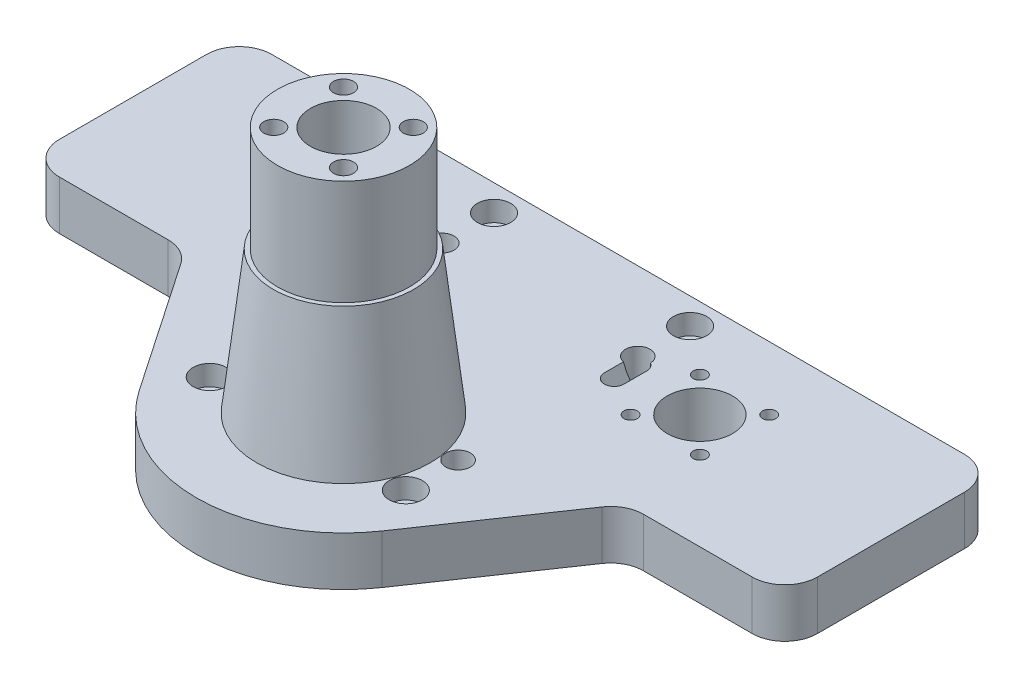
SolidWorks part; units mm, degrees
material "PLA Infill"
ref_plane "Front Plane" through (0, 0, 0) normal (0, 0, 1) x (1, 0, 0)
ref_plane "Top Plane" through (0, 0, 0) normal (0, 1, 0) x (1, 0, 0)
ref_plane "Right Plane" through (0, 0, 0) normal (1, 0, 0) x (0, 0, -1)
sketch "Sketch1" plane through (0, 0, 0) normal (0, 1, 0) x (1, 0, 0)
  line L0 (0, 0) -> (55, 54.0672) construction
  line L1 (55, 54.0672) -> (-55, 54.0672) construction
  line L2 (-55, 54.0672) -> (0, 0) construction
  line L3 (-79.7903, 37.1722) -> (-37.1854, -25.3425) construction
  line L4 (-55, 84.0672) -> (55, 84.0672)
  line L5 (37.1854, -25.3425) -> (79.7903, 37.1722) construction
  line L6 (-55, 84.0672) -> (-106, 84.0672)
  line L7 (-116, 74.0672) -> (-116, 29.0672)
  line L8 (-106, 19.0672) -> (-72.7378, 19.0672)
  line L9 (-64.4743, 14.6989) -> (-37.1854, -25.3425)
  line L10 (0, -1000) -> (0, 49000) construction
  line L11 (64.4743, 14.6989) -> (37.1854, -25.3425)
  line L12 (106, 19.0672) -> (72.7378, 19.0672)
  line L13 (116, 74.0672) -> (116, 29.0672)
  line L14 (55, 84.0672) -> (106, 84.0672)
  circle A0 centre (-55, 54.0672) radius 30 construction
  circle A1 centre (55, 54.0672) radius 30 construction
  circle A2 centre (0, 0) radius 45 construction
  arc A3 (-79.7903, 37.1722) -> (-55, 84.0672) centre (-55, 54.0672) cw construction
  arc A4 (55, 84.0672) -> (79.7903, 37.1722) centre (55, 54.0672) cw construction
  arc A5 (-37.1854, -25.3425) -> (37.1854, -25.3425) centre (0, 0) ccw
  arc A6 (-72.7378, 19.0672) -> (-64.4743, 14.6989) centre (-72.7378, 9.0672) cw
  arc A7 (-116, 29.0672) -> (-106, 19.0672) centre (-106, 29.0672) ccw
  arc A8 (-106, 84.0672) -> (-116, 74.0672) centre (-106, 74.0672) ccw
  arc A9 (72.7378, 19.0672) -> (64.4743, 14.6989) centre (72.7378, 9.0672) ccw
  arc A10 (116, 29.0672) -> (106, 19.0672) centre (106, 29.0672) cw
  arc A11 (106, 84.0672) -> (116, 74.0672) centre (106, 74.0672) cw
  point P23 (-67.4514, 19.0672)
  dimension "D3" = 60
  dimension "D4" = 90
  dimension "D5" = 10
  dimension "D6" = 61
  dimension "D1" = 110
  dimension "D2" = 77.125
  dimension "D7" = 35
extrude "Main Body" add sketch "Sketch1" along normal blind 15 contours A5 L11 A9 L12 A10 L13 A11 L14 L4 L6 A8 L7 A7 L8 A6 L9
sketch "Sketch3" plane through (0, 15, 0) normal (0, 1, 0) x (1, 0, 0)
  circle A0 centre (0, 0) radius 45 construction
  circle A1 centre (0, 0) radius 45 construction
  circle A2 centre (0, 0) radius 21.5
  dimension "D1" = 43
extrude "Front Extrusion" add sketch "Sketch3" along normal blind 75.7
ref_plane "First Bearing Section" through (0, 58.5, 0) normal (0, 1, 0) x (1, 0, 0)
sketch "Front Loft" plane through (0, 58.5, 0) normal (0, 1, 0) x (1, 0, 0)
  circle A0 centre (0, 0) radius 21.5
  dimension "D1" = 43
sketch "Back Loft" plane through (0, 15, 0) normal (0, 1, 0) x (1, 0, 0)
  circle A0 centre (0, 0) radius 26.5
  dimension "D1" = 53
loft "Lofted Taper" add profiles "Front Loft", "Back Loft" connector at (0, 58.5, 21.5) connector at (0, 15, 26.5)
sketch "Sketch4" plane through (0, 0, 0) normal (0, -1, 0) x (1, 0, 0)
  line L0 (0, -1000) -> (0, 49000) construction
  line L1 (-45, 0) -> (45, 0) construction
  line L2 (-85, -54.0672) -> (-25, -54.0672) construction
  line L3 (55, -54.0672) -> (-55, -54.0672) construction
  line L4 (-55, -24.0672) -> (-55, -84.0672) construction
  line L5 (-10.6773, 10.6773) -> (0, 0) construction
  line L6 (-10.6773, -10.6773) -> (0, 0) construction
  line L7 (-65.6066, -43.4606) -> (-55, -54.0672) construction
  line L8 (-106, -84.0672) -> (106, -84.0672) construction
  line L9 (106, -84.0672) -> (-106, -84.0672) construction
  line L10 (-30, -76.0672) -> (0, -76.0672) construction
  line L11 (-30, -76.0672) -> (-30, 10.9328) construction
  line L12 (-30, 10.9328) -> (0, 10.9328) construction
  line L13 (0, -76.0672) -> (0, 10.9328) construction
  circle A0 centre (55, -54.0672) radius 30 construction
  circle A1 centre (0, 0) radius 45 construction
  circle A2 centre (-55, -54.0672) radius 30 construction
  circle A3 centre (55, -54.0672) radius 30 construction
  circle A4 centre (0, 0) radius 45 construction
  circle A5 centre (-55, -54.0672) radius 30 construction
  circle A6 centre (0, 0) radius 10.1
  circle A7 centre (-55, -54.0672) radius 10
  circle A10 centre (-10.6773, 10.6773) radius 3.05
  circle A12 centre (-30, -60.0672) radius 3.75
  circle A13 centre (-10.6773, -10.6773) radius 3.05
  circle A14 centre (-65.6066, -43.4606) radius 2.05
  circle A15 centre (-65.6066, -64.6738) radius 2.05
  circle A16 centre (-44.3934, -64.6738) radius 2.05
  circle A17 centre (-44.3934, -43.4606) radius 2.05
  circle A18 centre (55, -54.0672) radius 10
  circle A19 centre (65.6066, -64.6738) radius 2.05
  circle A20 centre (44.3934, -64.6738) radius 2.05
  circle A21 centre (44.3934, -43.4606) radius 2.05
  circle A22 centre (65.6066, -43.4606) radius 2.05
  circle A23 centre (10.6773, -10.6773) radius 3.05
  circle A24 centre (10.6773, 10.6773) radius 3.05
  circle A25 centre (-30, -76.0672) radius 3.05
  circle A26 centre (-30, 10.9328) radius 3.05
  circle A27 centre (30, -76.0672) radius 3.05
  circle A28 centre (30, 10.9328) radius 3.05
  circle A29 centre (-30, -5.0672) radius 3.75
  circle A30 centre (30, -60.0672) radius 3.75
  circle A31 centre (30, -5.0672) radius 3.75
  dimension "D1" = 20.2
  dimension "D2" = 20
  dimension "D4" = 6.1
  dimension "D5" = 45
  dimension "D7" = 4.1
  dimension "D9" = 6.1
  dimension "D13" = 7.5
  dimension "D3" = 15.1
  dimension "D6" = 15
  dimension "D8" = 45
  dimension "D10" = 30
  dimension "D11" = 8
  dimension "D12" = 87
  dimension "D14" = 16
  dimension "D15" = 16
extrude "Bolt Holes" cut sketch "Sketch4" against normal through all
sketch "Sketch5" plane through (0, 0, 0) normal (0, -1, 0) x (1, 0, 0)
  line L0 (-14.2836, 7.0711) -> (-9.7707, 2.5582)
  line L1 (-7.0711, 14.2836) -> (-2.5582, 9.7707)
  line L2 (-10.6773, 10.6773) -> (0, 0) construction
  line L3 (-1000, 0) -> (49000, 0) construction
  line L4 (0, -1000) -> (0, 49000) construction
  line L5 (-14.2836, -7.0711) -> (-9.7707, -2.5582)
  line L6 (-7.0711, -14.2836) -> (-2.5582, -9.7707)
  line L7 (7.0711, -14.2836) -> (2.5582, -9.7707)
  line L8 (14.2836, -7.0711) -> (9.7707, -2.5582)
  line L9 (14.2836, 7.0711) -> (9.7707, 2.5582)
  line L10 (7.0711, 14.2836) -> (2.5582, 9.7707)
  circle A0 centre (-10.6773, 10.6773) radius 2 construction
  circle A1 centre (-10.6773, 10.6773) radius 5.1 construction
  circle A2 centre (0, 0) radius 10.1 construction
  arc A3 (-14.2836, 7.0711) -> (-7.0711, 14.2836) centre (-10.6773, 10.6773) cw
  circle A4 centre (0, 0) radius 10.1 construction
  arc A5 (-9.7707, 2.5582) -> (-2.5582, 9.7707) centre (0, 0) cw
  arc A6 (-14.2836, -7.0711) -> (-7.0711, -14.2836) centre (-10.6773, -10.6773) ccw
  arc A7 (-9.7707, -2.5582) -> (-2.5582, -9.7707) centre (0, 0) ccw
  arc A8 (14.2836, -7.0711) -> (7.0711, -14.2836) centre (10.6773, -10.6773) cw
  arc A9 (9.7707, -2.5582) -> (2.5582, -9.7707) centre (0, 0) cw
  arc A10 (14.2836, 7.0711) -> (7.0711, 14.2836) centre (10.6773, 10.6773) ccw
  arc A11 (9.7707, 2.5582) -> (2.5582, 9.7707) centre (0, 0) ccw
  dimension "D1" = 4
  dimension "D2" = 10.2
extrude "Bolt Recesses Rear" cut sketch "Sketch5" against normal blind 10
sketch "Sketch6" plane through (0, 15, 0) normal (0, 1, 0) x (1, 0, 0)
  circle A1 centre (30, 76.0672) radius 5.1
  circle A2 centre (-30, -10.9328) radius 3.05 construction
  circle A3 centre (30, -10.9328) radius 3.05 construction
  circle A4 centre (30, 76.0672) radius 3.05 construction
  circle A5 centre (-30, 76.0672) radius 3.05 construction
  circle A6 centre (-30, -10.9328) radius 3.05 construction
  circle A7 centre (30, -10.9328) radius 3.05 construction
  circle A8 centre (30, 76.0672) radius 3.05 construction
  circle A9 centre (-30, 76.0672) radius 3.05 construction
  circle A10 centre (-30, 76.0672) radius 5.1
  circle A11 centre (-30, -10.9328) radius 5.1
  circle A12 centre (30, -10.9328) radius 5.1
  dimension "D1" = 10.2
extrude "Bolt Recesses Front" cut sketch "Sketch6" against normal blind 6.2
sketch "Sketch7" plane through (0, 90.7, 0) normal (0, 1, 0) x (1, 0, 0)
  circle A0 centre (0, 0) radius 21.5 construction
  circle A1 centre (0, 0) radius 21.5
  circle A2 centre (0, 0) radius 20.2
  dimension "D1" = 40.4
extrude "Cut-Extrude1" cut sketch "Sketch7" against normal up to surface (32.2 mm away) up to plane "First Bearing Section"
sketch "Sketch8" plane through (0, 0, 0) normal (0, -1, 0) x (1, 0, 0)
  line L0 (0, -1000) -> (0, 49000) construction
  circle A0 centre (-65.6066, -64.6738) radius 2.05 construction
  circle A1 centre (-44.3934, -64.6738) radius 2.05 construction
  circle A2 centre (-44.3934, -43.4606) radius 2.05 construction
  circle A3 centre (-65.6066, -43.4606) radius 2.05 construction
  circle A4 centre (-65.6066, -64.6738) radius 2.05 construction
  circle A5 centre (-44.3934, -64.6738) radius 2.05 construction
  circle A6 centre (-44.3934, -43.4606) radius 2.05 construction
  circle A7 centre (-65.6066, -43.4606) radius 2.05 construction
  circle A8 centre (-65.6066, -43.4606) radius 3.55
  circle A9 centre (-44.3934, -43.4606) radius 3.55
  circle A10 centre (-44.3934, -64.6738) radius 3.55
  circle A11 centre (-65.6066, -64.6738) radius 3.55
  circle A12 centre (44.3934, -64.6738) radius 3.55
  circle A13 centre (44.3934, -43.4606) radius 3.55
  circle A14 centre (65.6066, -64.6738) radius 3.55
  circle A15 centre (65.6066, -43.4606) radius 3.55
  dimension "D1" = 7.1
extrude "Motor bolt head recesses" cut sketch "Sketch8" against normal blind 4.1
sketch "Sketch9" plane through (0, 0, 0) normal (0, -1, 0) x (1, 0, 0)
  line L0 (0, -1000) -> (0, 49000) construction
  line L1 (-116, -74.0672) -> (-116, -29.0672) construction
  line L2 (106, -84.0672) -> (-106, -84.0672) construction
  line L4 (-111, -75.0672) -> (-41, -75.0672) construction
  line L5 (-111, -75.0672) -> (-111, -28.0672) construction
  line L6 (-111, -28.0672) -> (-41, -28.0672) construction
  line L7 (-41, -75.0672) -> (-41, -28.0672) construction
  circle A0 centre (-111, -75.0672) radius 2
  circle A1 centre (-111, -28.0672) radius 2
  circle A2 centre (-41, -28.0672) radius 2
  circle A3 centre (-41, -75.0672) radius 2
  circle A4 centre (41, -75.0672) radius 2
  circle A5 centre (111, -75.0672) radius 2
  circle A6 centre (41, -28.0672) radius 2
  circle A7 centre (111, -28.0672) radius 2
  dimension "D3" = 4
  dimension "D1" = 5
  dimension "D2" = 9
  dimension "D4" = 70
  dimension "D5" = 47
extrude "Heat-set insert holes" cut sketch "Sketch9" against normal blind 6
sketch "Sketch10" plane through (0, 0, 0) normal (0, -1, 0) x (1, 0, 0)
  line L0 (0, -1000) -> (0, 49000) construction
  line L1 (-116, -74.0672) -> (-116, -29.0672) construction
  line L2 (106, -84.0672) -> (-106, -84.0672) construction
  line L4 (-101.5, -76.5672) -> (-51.5, -76.5672) construction
  line L5 (-101.5, -76.5672) -> (-101.5, -26.5672) construction
  line L6 (-101.5, -26.5672) -> (-51.5, -26.5672) construction
  line L7 (-51.5, -76.5672) -> (-51.5, -26.5672) construction
  circle A0 centre (-101.5, -76.5672) radius 1.6
  circle A1 centre (-101.5, -26.5672) radius 1.6
  circle A2 centre (-51.5, -26.5672) radius 1.6
  circle A3 centre (-51.5, -76.5672) radius 1.6
  circle A4 centre (101.5, -76.5672) radius 1.6
  circle A5 centre (51.5, -76.5672) radius 1.6
  circle A6 centre (51.5, -26.5672) radius 1.6
  circle A7 centre (101.5, -26.5672) radius 1.6
  dimension "D1" = 3.2
  dimension "D2" = 14.5
  dimension "D3" = 7.5
  dimension "D4" = 50
  dimension "D5" = 50
extrude "PCB Heat-set insert holes" cut sketch "Sketch10" against normal blind 4
sketch "Sketch11" plane through (0, 0, -84.0672) normal (0, 0, -1) x (-1, 0, 0)
  line L0 (0, -1000) -> (0, 49000) construction
  line L1 (-106, 0) -> (106, 0) construction
  circle A0 centre (-20, 7.5) radius 2
  circle A2 centre (20, 7.5) radius 2
  dimension "D1" = 4
  dimension "D2" = 7.5
  dimension "D3" = 20
extrude "Cut-Extrude2" cut sketch "Sketch11" against normal blind 6
sketch "Motor wires shape front" plane through (0, 15, 0) normal (0, 1, 0) x (1, 0, 0)
  line L0 (0, -1000) -> (0, 49000) construction
  line L1 (-32.2679, 57.5672) -> (-32.2679, 50.5672) construction
  line L2 (-29.2679, 57.5672) -> (-29.2679, 50.5672)
  line L3 (-35.2679, 57.5672) -> (-35.2679, 50.5672)
  line L4 (-55, 54.0672) -> (-32, 54.0672) construction
  line L8 (-55, 77.0672) -> (-55, 31.0672) construction
  circle A0 centre (-55, 54.0672) radius 23 construction
  arc A1 (-29.2679, 57.5672) -> (-35.2679, 57.5672) centre (-32.2679, 57.5672) ccw
  arc A2 (-35.2679, 50.5672) -> (-29.2679, 50.5672) centre (-32.2679, 50.5672) ccw
  point P8 (-32.2679, 54.0672)
  dimension "D1" = 46
  dimension "D3" = 3
  dimension "D2" = 7
  dimension "D4" = 90
sketch "Motor wires shape back" plane through (0, 0, 0) normal (0, -1, 0) x (1, 0, 0)
  line L0 (-38.5931, -52.3172) -> (-38.5931, -55.8172) construction
  line L1 (-36.5931, -52.3172) -> (-36.5931, -55.8172)
  line L2 (-40.5931, -52.3172) -> (-40.5931, -55.8172)
  line L3 (-55, -54.0672) -> (-38.5931, -54.0672) construction
  line L4 (-55, -77.0672) -> (-55, -31.0672) construction
  line L5 (0, 201000) -> (0, -249000) construction
  line L6 (0, 201000) -> (0, -249000) construction
  arc A1 (-36.5931, -52.3172) -> (-40.5931, -52.3172) centre (-38.5931, -52.3172) ccw
  arc A2 (-40.5931, -55.8172) -> (-36.5931, -55.8172) centre (-38.5931, -55.8172) ccw
  circle A3 centre (-55, -54.0672) radius 16.5 construction
  point P2 (0, 0)
  point P4 (-38.5931, -54.0672)
  point P14 (0, 0)
  dimension "D3" = 2
  dimension "D4" = 33
  dimension "D1" = 90
  dimension "D2" = 3.5
loft "Cut-Loft4" cut section "Motor wires shape front" section "Motor wires shape back" connector at (-29.2679, 15, -57.5672) connector at (-36.5931, 0, -55.8172)
mirror "Mirror1" about plane through (0, 0, 0) normal (1, 0, 0) of "Cut-Loft4"
